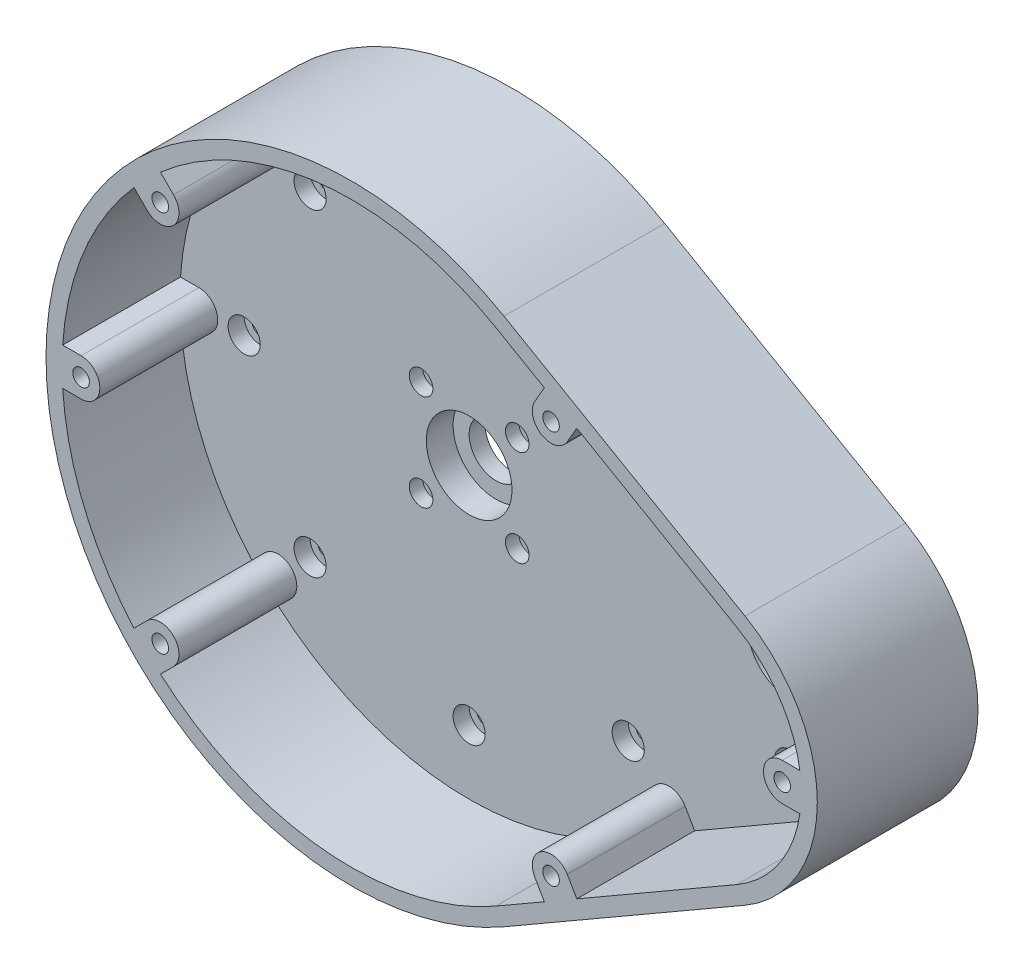
SolidWorks part; units mm, degrees
ref_plane "Front Plane" through (0, 0, 0) normal (0, 0, 1) x (1, 0, 0)
ref_plane "Top Plane" through (0, 0, 0) normal (0, 1, 0) x (1, 0, 0)
ref_plane "Right Plane" through (0, 0, 0) normal (1, 0, 0) x (0, 0, -1)
sketch "Sketch1" plane through (0, 0, 0) normal (0, 0, 1) x (1, 0, 0)
  line L0 (-30, 0) -> (30, 0) construction
  line L3 (-1.5, 49.3634) -> (43.5, 23.3827)
  line L4 (-1.5, -49.3634) -> (43.5, -23.3827)
  circle A0 centre (-30, 0) radius 57 construction
  circle A1 centre (30, 0) radius 27 construction
  circle A4 centre (-30, 0) radius 46.5 construction
  circle A5 centre (30, 0) radius 16.5 construction
  arc A6 (-1.5, 49.3634) -> (-1.5, -49.3634) centre (-30, 0) ccw
  arc A7 (43.5, 23.3827) -> (43.5, -23.3827) centre (30, 0) cw
  point P4 (0, 0)
extrude "Boss-Extrude1" add sketch "Sketch1" along normal blind 30 contours L4 A7 L3 A6
sketch "Sketch3" plane through (0, 0, 30) normal (0, 0, 1) x (1, 0, 0)
  line L3 (6.7696, 36.7696) -> (-66.7696, -36.7696) construction
  line L4 (-66.7696, -36.7696) -> (-65.6735, -35.6735) construction
  line L7 (-82, 0) -> (-80.45, 0) construction
  line L8 (50.45, 3.5259) -> (53.7396, 3.5259)
  line L9 (50.45, -3.4741) -> (53.7472, -3.4741)
  line L10 (-4, 45.0333) -> (41, 19.0526) construction
  line L11 (-4, -45.0333) -> (41, -19.0526) construction
  line L29 (-80.45, 3.5) -> (-83.8865, 3.5)
  line L30 (-80.45, -3.5) -> (-83.8865, -3.5)
  line L34 (-68.1484, -33.1987) -> (-63.1987, -38.1484) construction
  line L36 (27.2243, -57.2243) -> (-87.2243, 57.2243) construction
  line L37 (-66.7696, 36.7696) -> (-65.6735, 35.6735) construction
  line L38 (-68.1484, 33.1987) -> (-63.1987, 38.1484) construction
  line L39 (-63.1987, 38.1484) -> (-65.6286, 40.5784)
  line L40 (-68.1484, 33.1987) -> (-70.5784, 35.6286)
  line L41 (-68.1484, -33.1987) -> (-70.5784, -35.6286)
  line L45 (8.0666, 38.0666) -> (7.2916, 36.7243) construction
  line L46 (10.3227, 34.9743) -> (4.2606, 38.4743) construction
  line L49 (8.0666, -38.0666) -> (7.2916, -36.7243) construction
  line L50 (4.2606, -38.4743) -> (10.3227, -34.9743) construction
  line L51 (10.3227, -34.9743) -> (12.0977, -38.0487)
  line L52 (4.2606, -38.4743) -> (6.0356, -41.5487)
  line L53 (42, -20.7846) -> (12.0977, -38.0487)
  line L56 (-3, -46.7654) -> (6.0356, -41.5487)
  line L57 (-65.6286, -40.5784) -> (-63.1987, -38.1484)
  line L58 (42, 20.7846) -> (-3, 46.7654) construction
  line L59 (10.3227, 34.9743) -> (12.0977, 38.0487)
  line L60 (4.2606, 38.4743) -> (6.0356, 41.5487)
  line L61 (-3, 46.7654) -> (6.0356, 41.5487)
  line L62 (12.0977, 38.0487) -> (42, 20.7846)
  line L63 (-30, 0) -> (7.2916, 36.7243) construction
  circle A6 centre (-30, 0) radius 52 construction
  circle A7 centre (30, 0) radius 22 construction
  arc A12 (50.45, -3.4741) -> (50.45, 3.5259) centre (50.45, 0.0259) cw
  circle A13 centre (50.45, 0.0259) radius 1.55
  arc A22 (42, 20.7846) -> (53.7396, 3.5259) centre (30, 0) cw
  arc A23 (53.7472, -3.4741) -> (42, -20.7846) centre (30, 0) cw
  arc A30 (-65.6286, 40.5784) -> (-3, 46.7654) centre (-30, 0) cw
  arc A32 (-70.5784, 35.6286) -> (-83.8865, 3.5) centre (-30, 0) ccw
  circle A41 centre (-80.45, 0) radius 1.55
  arc A42 (-80.45, 3.5) -> (-80.45, -3.5) centre (-80.45, 0) cw
  circle A44 centre (-65.6735, 35.6735) radius 1.55
  arc A45 (-63.1987, 38.1484) -> (-68.1484, 33.1987) centre (-65.6735, 35.6735) cw
  circle A51 centre (7.2916, -36.7243) radius 1.55
  arc A52 (4.2606, -38.4743) -> (10.3227, -34.9743) centre (7.2916, -36.7243) cw
  arc A53 (-83.8865, -3.5) -> (-70.5784, -35.6286) centre (-30, 0) ccw
  arc A54 (-65.6286, -40.5784) -> (-3, -46.7654) centre (-30, 0) ccw
  circle A55 centre (-65.6735, -35.6735) radius 1.55
  arc A56 (-68.1484, -33.1987) -> (-63.1987, -38.1484) centre (-65.6735, -35.6735) cw
  circle A57 centre (-30, 0) radius 54 construction
  circle A58 centre (7.2916, 36.7243) radius 1.55
  arc A59 (4.2606, 38.4743) -> (10.3227, 34.9743) centre (7.2916, 36.7243) ccw
  point P10 (-30, 0)
  point P20 (-30, 0)
  point P22 (-30, 0)
  point P32 (-30, 0)
  point P35 (-30, 0)
  point P37 (-30, 0)
  point P39 (-30, 0)
  point P45 (-65.6735, 35.6735)
  point P51 (-30, 0)
  point P56 (-65.6735, -35.6735)
  point P59 (-30, 0)
  point P68 (7.2916, 36.7243)
  point P85 (7.2916, -36.7243)
extrude "Cut-Extrude1" cut sketch "Sketch3" against normal blind 22
sketch "Sketch5" plane through (0, 0, 0) normal (0, 0, -1) x (-1, 0, 0)
  circle A12 centre (65.6735, 35.6735) radius 1.55
  circle A13 centre (80.45, 0) radius 1.55
  circle A15 centre (-50.45, 0.0259) radius 1.55
  circle A16 centre (-7.2916, -36.7243) radius 1.55
  circle A18 centre (65.6735, -35.6735) radius 1.55
  circle A19 centre (-7.2916, 36.7243) radius 1.55
extrude "Cut-Extrude2" cut sketch "Sketch5" against normal blind 30
sketch "Sketch6" plane through (0, 0, 0) normal (0, 0, -1) x (-1, 0, 0)
  circle A12 centre (-50.45, 0.0259) radius 3
  circle A13 centre (-7.2916, -36.7243) radius 3
  circle A15 centre (80.45, 0) radius 3
  circle A16 centre (65.6735, 35.6735) radius 3
  circle A18 centre (65.6735, -35.6735) radius 3
  circle A19 centre (-7.2916, 36.7243) radius 3
extrude "Cut-Extrude3" cut sketch "Sketch6" against normal blind 5
sketch "Sketch7" plane through (0, 0, 8) normal (0, 0, 1) x (1, 0, 0)
  line L0 (-30, 0) -> (30, 0) construction
  circle A4 centre (-30, 0) radius 8
  circle A6 centre (30, 0) radius 8
extrude "Cut-Extrude10" cut sketch "Sketch7" against normal blind 5
sketch "Sketch8" plane through (0, 0, 8) normal (0, 0, 1) x (1, 0, 0)
  line L0 (-30, 0) -> (-38.9803, 8.9803) construction
  circle A0 centre (-30, 0) radius 5
  circle A1 centre (-30, 0) radius 12.7 construction
  circle A2 centre (-38.9803, 8.9803) radius 1.05
  circle A3 centre (-21.0197, 8.9803) radius 1.05
  circle A4 centre (-21.0197, -8.9803) radius 1.05
  circle A5 centre (-38.9803, -8.9803) radius 1.05
  point P7 (-30, 0)
  point P10 (-30, 0)
  point P17 (-30, 0)
  dimension "D1" = 4
extrude "Cut-Extrude7" cut sketch "Sketch8" against normal blind 8
sketch "Sketch9" plane through (0, 0, 8) normal (0, 0, 1) x (1, 0, 0)
  circle A0 centre (-38.9803, 8.9803) radius 2.2
  circle A1 centre (-21.0197, 8.9803) radius 2.2
  circle A2 centre (-21.0197, -8.9803) radius 2.2
  circle A3 centre (-38.9803, -8.9803) radius 2.2
  point P12 (-30, 0)
  dimension "D1" = 4
extrude "Cut-Extrude8" cut sketch "Sketch9" against normal blind 2.5
sketch "Sketch10" plane through (0, 0, 30) normal (0, 0, 1) x (1, 0, 0)
  line L0 (-3.0003, 46.7655) -> (42, 20.7849)
  line L2 (-3.0003, -46.7655) -> (42, -20.7849)
  line L3 (-4, 45.0333) -> (41, 19.0526)
  line L4 (-4, -45.0333) -> (41, -19.0526)
  circle A0 centre (-30, 0) radius 54 construction
  circle A1 centre (30, 0) radius 24.0003 construction
  arc A2 (-3.0003, 46.7655) -> (-3.0003, -46.7655) centre (-30, 0) ccw
  arc A3 (42, 20.7849) -> (42, -20.7849) centre (30, 0) cw
  circle A4 centre (-30, 0) radius 52 construction
  circle A5 centre (30, 0) radius 22 construction
  arc A6 (41, 19.0526) -> (41, -19.0526) centre (30, 0) cw
  arc A7 (-4, 45.0333) -> (-4, -45.0333) centre (-30, 0) ccw
sketch "Sketch11" plane through (0, 0, 8) normal (0, 0, 1) x (1, 0, 0)
  line L0 (-30, 0) -> (-0.3015, 29.6985) construction
  line L1 (30, -19) -> (30, 19) construction
  line L2 (30, 0) -> (42, 0) construction
  circle A0 centre (-30, 0) radius 42 construction
  circle A1 centre (-0.3015, 29.6985) radius 1.55
  circle A2 centre (-30, 42) radius 1.55
  circle A3 centre (-59.6985, 29.6985) radius 1.55
  circle A4 centre (-72, 0) radius 1.55
  circle A5 centre (-59.6985, -29.6985) radius 1.55
  circle A6 centre (-30, -42) radius 1.55
  circle A7 centre (-0.3015, -29.6985) radius 1.55
  circle A8 centre (30, 19) radius 1.55
  circle A9 centre (30, -19) radius 1.55
  circle A10 centre (42, 0) radius 1.55
  point P19 (-30, 0)
  point P24 (30, 0)
  dimension "D1" = 7
extrude "Cut-Extrude11" cut sketch "Sketch11" against normal blind 8
sketch "Sketch12" plane through (0, 0, 8) normal (0, 0, 1) x (1, 0, 0)
  line L0 (-0.3015, 29.6985) -> (-30, 0) construction
  circle A0 centre (-0.3015, 29.6985) radius 3
  circle A1 centre (-30, 42) radius 3
  circle A2 centre (-59.6985, 29.6985) radius 3
  circle A3 centre (-72, 0) radius 3
  circle A4 centre (-59.6985, -29.6985) radius 3
  circle A5 centre (-30, -42) radius 3
  circle A6 centre (-0.3015, -29.6985) radius 3
  circle A7 centre (30, 19) radius 3
  circle A8 centre (42, 0) radius 3
  circle A9 centre (30, -19) radius 3
  point P20 (-30, 0)
  dimension "D1" = 7
extrude "Cut-Extrude12" cut sketch "Sketch12" against normal blind 3
